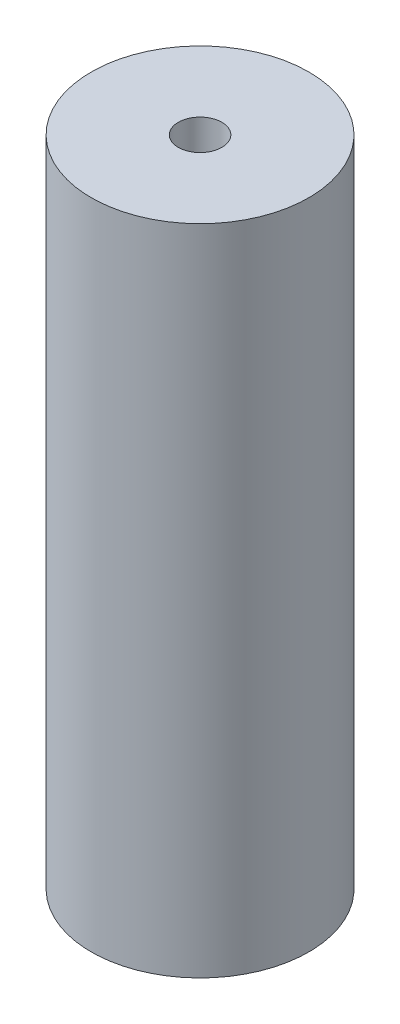
SolidWorks part; units mm, degrees
ref_plane "Front Plane" through (0, 0, 0) normal (0, 0, 1) x (1, 0, 0)
ref_plane "Top Plane" through (0, 0, 0) normal (0, 1, 0) x (1, 0, 0)
ref_plane "Right Plane" through (0, 0, 0) normal (1, 0, 0) x (0, 0, -1)
sketch "Sketch1" plane through (0, 0, 0) normal (0, 0, 1) x (1, 0, 0)
  line L0 (0, 0) -> (0, 5.7533) construction
  line L1 (-0.5, 15) -> (-0.5, 5)
  line L2 (-0.5, 5) -> (-1.4, 5)
  line L3 (-1.4, 5) -> (-1.4, 0)
  line L4 (-1.4, 0) -> (-2.5, 0)
  line L5 (-2.5, 0) -> (-2.5, 15)
  line L6 (-2.5, 15) -> (-0.5, 15)
  dimension "D1" = 2.8
  dimension "D2" = 5
  dimension "D3" = 1
  dimension "D4" = 10
  dimension "D5" = 5
revolve "Revolve1" add sketch "Sketch1" angle 360 about L0
